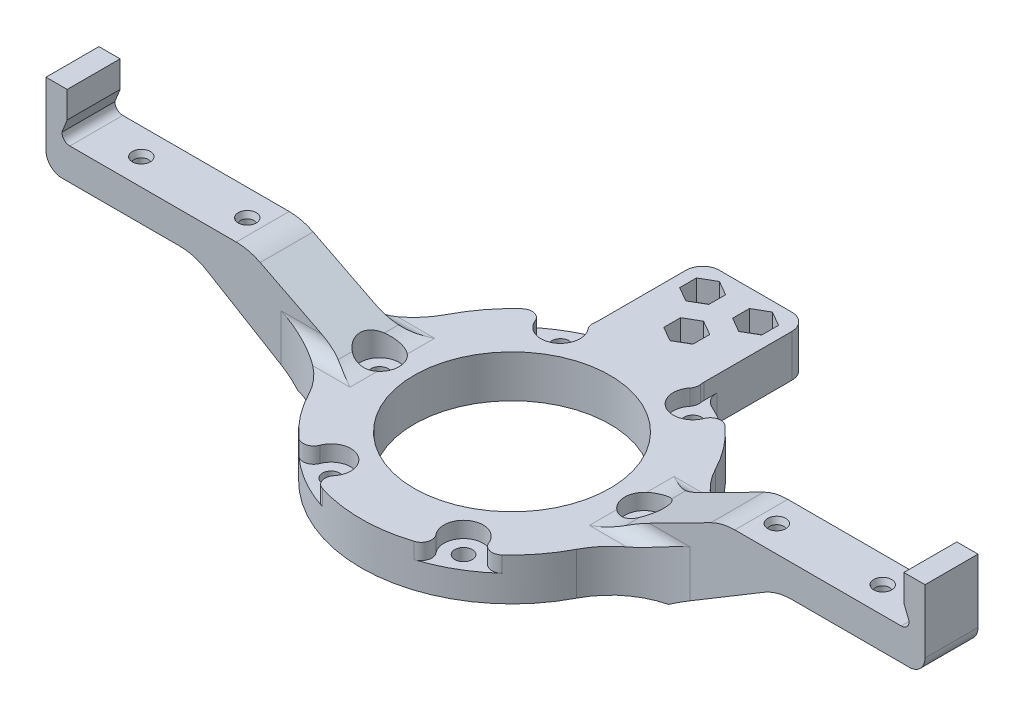
SolidWorks part; units mm, degrees
ref_plane "前视基准面" through (0, 0, 0) normal (0, 0, 1) x (1, 0, 0)
ref_plane "上视基准面" through (0, 0, 0) normal (0, 1, 0) x (1, 0, 0)
ref_plane "右视基准面" through (0, 0, 0) normal (1, 0, 0) x (0, 0, -1)
other "Configuration Table"
sketch "草图1" plane through (0, 0, 0) normal (0, 1, 0) x (1, 0, 0)
  circle A0 centre (0, 0) radius 28.5
extrude "凸台-拉伸1" add sketch "草图1" along normal blind 8
sketch "草图2" plane through (0, 0, 0) normal (0, 0, 1) x (1, 0, 0)
  line L0 (-78.5, 18) -> (-47.0799, 18)
  line L1 (-83, 18) -> (-83, 15)
  line L2 (-80, 12) -> (-57.7698, 12)
  line L3 (0, 0) -> (-35, 0)
  line L4 (-35, 0) -> (-52.6249, 10.5749)
  line L5 (-42.5509, 16.9156) -> (-27.1347, 9.0844)
  line L6 (28.5, 8) -> (-28.5, 8) construction
  line L7 (27.1347, 9.0844) -> (42.5509, 16.9156)
  line L8 (83, 18) -> (83, 15)
  line L9 (80, 12) -> (57.7698, 12)
  line L10 (0, 0) -> (35, 0)
  line L11 (35, 0) -> (52.6249, 10.5749)
  line L12 (47.0799, 18) -> (78.5, 18)
  line L13 (-22.6057, 8) -> (22.6057, 8)
  line L14 (-83, 18) -> (-83, 27)
  line L15 (-83, 27) -> (-80, 27)
  line L17 (83, 18) -> (83, 27)
  line L18 (83, 27) -> (80, 27)
  line L20 (-80, 27) -> (-79, 27)
  line L21 (-79, 27) -> (-79, 22)
  line L22 (-79, 22) -> (-80, 19.5)
  line L23 (80, 27) -> (79, 27)
  line L24 (79, 27) -> (79, 22)
  line L25 (79, 22) -> (80, 19.5)
  arc A2 (-42.5509, 16.9156) -> (-47.0799, 18) centre (-47.0799, 8) ccw
  arc A3 (-52.6249, 10.5749) -> (-57.7698, 12) centre (-57.7698, 2) ccw
  arc A4 (52.6249, 10.5749) -> (57.7698, 12) centre (57.7698, 2) cw
  arc A5 (47.0799, 18) -> (42.5509, 16.9156) centre (47.0799, 8) ccw
  arc A6 (-80, 19.5) -> (-78.5, 18) centre (-78.5, 19.5) ccw
  arc A7 (78.5, 18) -> (80, 19.5) centre (78.5, 19.5) ccw
  arc A8 (83, 15) -> (80, 12) centre (80, 15) cw
  arc A9 (-83, 15) -> (-80, 12) centre (-80, 15) ccw
  arc A10 (27.1347, 9.0844) -> (22.6057, 8) centre (22.6057, 18) cw
  arc A11 (-27.1347, 9.0844) -> (-22.6057, 8) centre (-22.6057, 18) ccw
  point P18 (25, 8)
  point P22 (-25, 8)
  point P31 (44.6855, 18)
  dimension "D1" = 10
  dimension "D2" = 10
  dimension "D3" = 1.5
  dimension "D4" = 3
extrude "凸台-拉伸2" add sketch "草图2" along normal mid plane 10
fillet "圆角1" radius 15 4 edges at (28.058, 4, -5) (28.058, 4, 5) (-28.058, 4, -5) (-28.058, 4, 5)
fillet "圆角2" radius 3 4 edges at (30.6177, 8, 5) (-30.6177, 8, 5) (-30.6177, 8, -5) (30.6177, 8, -5)
sketch "草图3" plane through (0, 18, 0) normal (0, 1, 0) x (1, 0, 0)
  circle A0 centre (-25, 0) radius 1.65
  circle A1 centre (-12.5, 21.6506) radius 1.65
  circle A2 centre (12.5, 21.6506) radius 1.65
  circle A3 centre (25, 0) radius 1.65
  circle A4 centre (12.5, -21.6506) radius 1.65
  circle A5 centre (-12.5, -21.6506) radius 1.65
  point P14 (0, 0)
  dimension "D1" = 6
extrude "切除-拉伸1" cut sketch "草图3" against normal up to surface (18 mm away) up to face at (0, 0, 0)
sketch "草图4" plane through (0, 18, 0) normal (0, 1, 0) x (1, 0, 0)
  circle A0 centre (-25, 0) radius 3.7
  circle A1 centre (-12.5, 21.6506) radius 3.7
  circle A2 centre (12.5, 21.6506) radius 3.7
  circle A3 centre (25, 0) radius 3.7
  circle A4 centre (12.5, -21.6506) radius 3.7
  circle A5 centre (-12.5, -21.6506) radius 3.7
  point P15 (0, 0)
  dimension "D1" = 6
extrude "切除-拉伸2" cut sketch "草图4" against normal blind 13
fillet "圆角3" radius 2 8 edges at (15.3449, 6.5, -24.0163) (13.1263, 6.5, -25.2972) (-13.1263, 6.5, -25.2972) (-15.3449, 6.5, -24.0163) (15.3449, 6.5, 24.0163) (13.1263, 6.5, 25.2972) (-13.1263, 6.5, 25.2972) (-15.3449, 6.5, 24.0163)
sketch "草图5" plane through (0, 8, 0) normal (0, 1, 0) x (1, 0, 0)
  circle A0 centre (0, 0) radius 18.5
extrude "切除-拉伸3" cut sketch "草图5" against normal up to surface (8 mm away) up to face at (-25, 0, 1.65)
sketch "草图6" plane through (0, 18, 0) normal (0, 1, 0) x (1, 0, 0)
  circle A0 centre (-70, 0) radius 1.3
  circle A1 centre (-50, 0) radius 1.3
  circle A2 centre (50, 0) radius 1.3
  circle A3 centre (70, 0) radius 1.3
extrude "切除-拉伸4" cut sketch "草图6" against normal up to surface (18 mm away) up to face at (0, 0, 18.5)
chamfer "倒角1" distance 0.4 angle 70 4 edges at (70, 18, 1.3) (50, 18, 1.3) (-50, 18, 1.3) (-70, 18, 1.3) first distance on face at (50, 18, 1.3) first distance on face at (-70, 18, 1.3)
sketch "草图7" plane through (0, 0, 0) normal (0, 1, 0) x (1, 0, 0)
  line L0 (-10, 46) -> (10, 46)
  line L1 (-10, 46) -> (-10, 25)
  line L2 (10, 46) -> (10, 25)
  line L3 (10, 25) -> (-10, 25)
extrude "凸台-拉伸3" add sketch "草图7" along normal blind 8
fillet "圆角4" radius 3 2 edges at (-10, 2.5, -26.688) (10, 2.5, -26.688)
fillet "圆角5" radius 5 2 edges at (10, 6.5, -25.7742) (-10, 6.5, -25.7742)
fillet "圆角6" radius 3.15 2 edges at (-10, 4, -46) (10, 4, -46)
sketch "草图8" plane through (0, 8, 0) normal (0, 1, 0) x (1, 0, 0)
  circle A0 centre (-5, 41) radius 1.65
  circle A1 centre (5, 41) radius 1.65
  circle A2 centre (0, 33) radius 1.65
extrude "切除-拉伸5" cut sketch "草图8" against normal up to surface (8 mm away) up to face at (0, 0, -17.1672)
sketch "草图9" plane through (0, 8, 0) normal (0, 1, 0) x (1, 0, 0)
  line L1 (-5, 44.1754) -> (-7.75, 42.5877)
  line L2 (-7.75, 42.5877) -> (-7.75, 39.4123)
  line L3 (-7.75, 39.4123) -> (-5, 37.8246)
  line L4 (-5, 37.8246) -> (-2.25, 39.4123)
  line L5 (-2.25, 39.4123) -> (-2.25, 42.5877)
  line L6 (-2.25, 42.5877) -> (-5, 44.1754)
  line L7 (5, 44.1754) -> (2.25, 42.5877)
  line L8 (2.25, 42.5877) -> (2.25, 39.4123)
  line L9 (2.25, 39.4123) -> (5, 37.8246)
  line L10 (5, 37.8246) -> (7.75, 39.4123)
  line L11 (7.75, 39.4123) -> (7.75, 42.5877)
  line L12 (7.75, 42.5877) -> (5, 44.1754)
  line L13 (0, 36.1754) -> (-2.75, 34.5877)
  line L14 (-2.75, 34.5877) -> (-2.75, 31.4123)
  line L15 (-2.75, 31.4123) -> (0, 29.8246)
  line L16 (0, 29.8246) -> (2.75, 31.4123)
  line L17 (2.75, 31.4123) -> (2.75, 34.5877)
  line L18 (2.75, 34.5877) -> (0, 36.1754)
  circle A0 centre (-5, 41) radius 2.75 construction
  circle A1 centre (5, 41) radius 2.75 construction
  circle A2 centre (0, 33) radius 2.75 construction
  dimension "D1" = 5.5
  dimension "D2" = 5.5
  dimension "D3" = 5.5
extrude "切除-拉伸6" cut sketch "草图9" against normal blind 4
